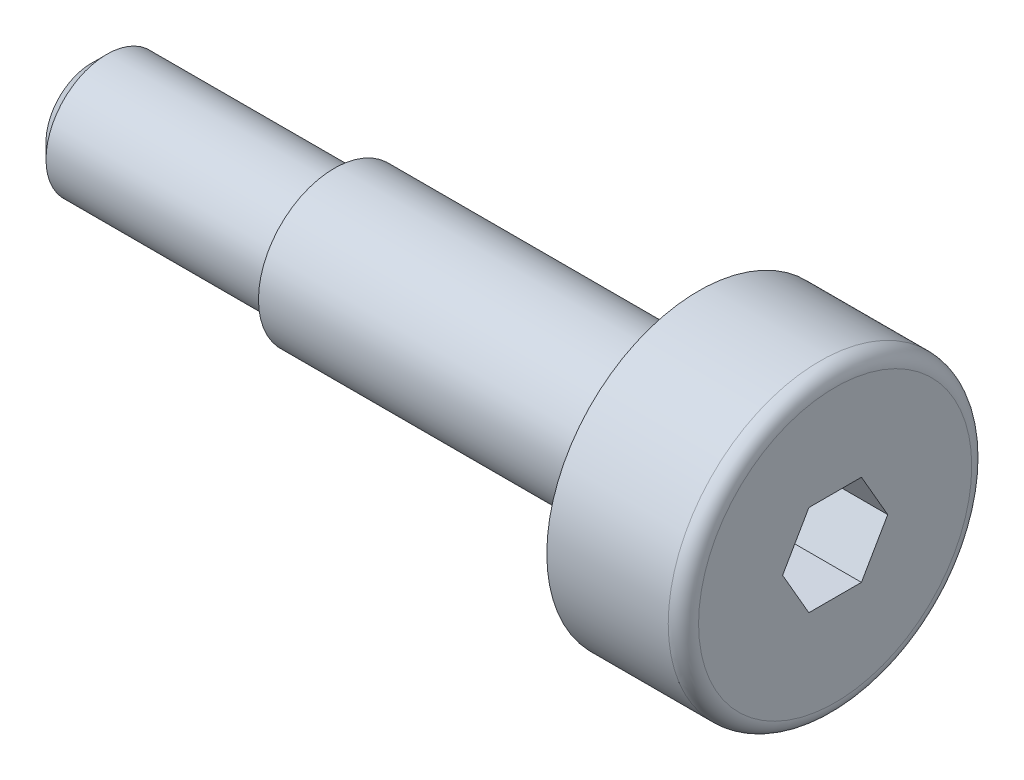
SolidWorks part; units mm, degrees
material "AISI 1020"
ref_plane "XY (Front)" through (0, 0, 0) normal (0, 0, 1) x (1, 0, 0)
ref_plane "XZ (Top)" through (0, 0, 0) normal (0, 1, 0) x (1, 0, 0)
ref_plane "YZ (Right)" through (0, 0, 0) normal (1, 0, 0) x (0, 0, -1)
ref_axis "X" through (-25.2, 0, 0) along (1, 0, 0)
ref_axis "Y" through (0, 5.5, 0) along (0, -1, 0)
ref_axis "Z" through (0, 0, -5.5) along (0, 0, 1)
sketch "Sketch1" plane through (0, 0, 0) normal (0, 0, 1) x (1, 0, 0)
  line L0 (0, 0) -> (0, 4.5)
  line L1 (-0.5, 5) -> (-4.5, 5)
  line L2 (-4.5, 5) -> (-4.5, 2.5)
  line L3 (-4.5, 2.5) -> (-16.5, 2.5)
  line L4 (-16.5, 2.5) -> (-16.5, 2)
  line L5 (-16.5, 2) -> (-24.5, 2)
  line L6 (-24.5, 2) -> (-24.5, 0)
  line L7 (-24.5, 0) -> (0, 0)
  line L8 (0, 0) -> (5.7531, 0) construction
  arc A0 (0, 4.5) -> (-0.5, 5) centre (-0.5, 4.5) ccw
  dimension "R" = 0.5
  dimension "d3" = 10
  dimension "d1" = 5
  dimension "M" = 4
  dimension "l3" = 4.5
  dimension "l1" = 12
  dimension "l2" = 8
revolve "Revolve1" add sketch "Sketch1" angle 360 about L8
chamfer "Chamfer1" distance 0.5 angle 45 1 edges at (-24.5, 0, 2)
sketch "Sketch2" plane through (0, 0, 0) normal (1, 0, 0) x (0, 0, -1)
  line L1 (1.7321, 0) -> (0.866, 1.5)
  line L2 (0.866, 1.5) -> (-0.866, 1.5)
  line L3 (-0.866, 1.5) -> (-1.7321, 0)
  line L4 (-1.7321, 0) -> (-0.866, -1.5)
  line L5 (-0.866, -1.5) -> (0.866, -1.5)
  line L6 (0.866, -1.5) -> (1.7321, 0)
  circle A0 centre (0, 0) radius 1.5 construction
  dimension "AF" = 3
extrude "Cut-Extrude1" cut sketch "Sketch2" against normal blind 2.4
